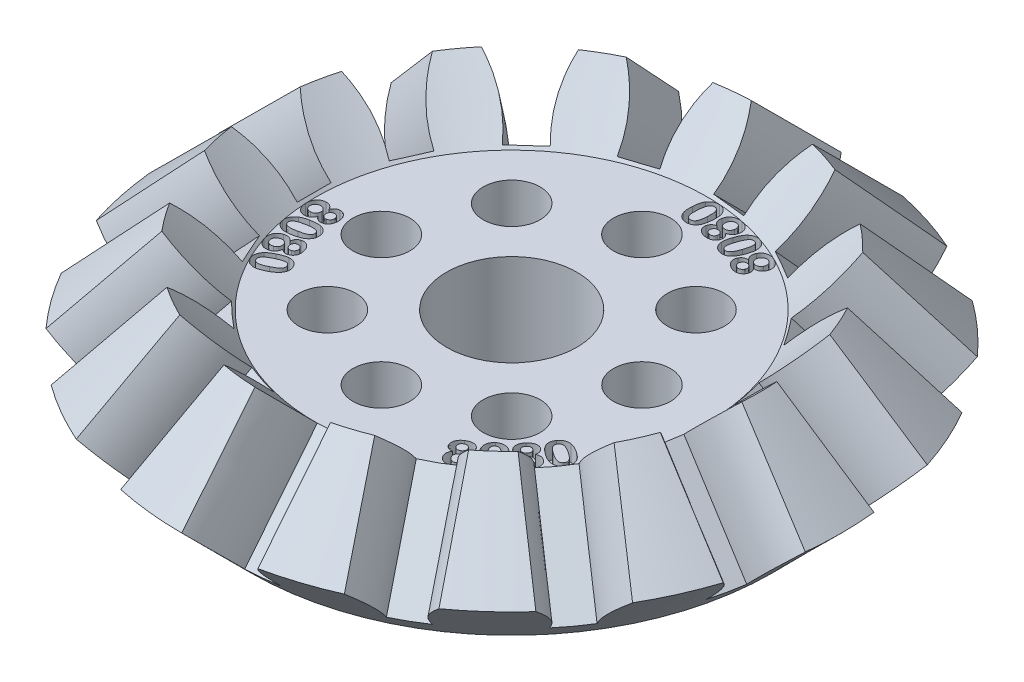
SolidWorks part; units mm, degrees
ref_plane "Front Plane" through (0, 0, 0) normal (0, 0, 1) x (1, 0, 0)
ref_plane "Top Plane" through (0, 0, 0) normal (0, 1, 0) x (1, 0, 0)
ref_plane "Right Plane" through (0, 0, 0) normal (1, 0, 0) x (0, 0, -1)
sketch "Sketch2" plane through (0, 0, 0) normal (0, 0, 1) x (1, 0, 0)
  line L6 (0, 0) -> (0, 6)
  line L7 (0, 0) -> (-16, 0)
  line L8 (0, 6) -> (-12, 6)
  line L9 (-16, 0) -> (-20.2426, 4.2426)
  line L14 (-20.2426, 4.2426) -> (-15.2426, 9.2426)
  line L15 (-12, 6) -> (-15.2426, 9.2426)
  dimension "D1" = 6
  dimension "D2" = 16
  dimension "D3" = 12
  dimension "D4" = 45
  dimension "D5" = 6
revolve "Revolve4" add sketch "Sketch2" angle 360 about L6
sketch "Sketch3" plane through (0, 0, 0) normal (0, 0, 1) x (1, 0, 0)
  line L0 (0, 0) -> (0, 24.4853) construction
  line L1 (0, 24.4853) -> (0, -16.6359) construction
  line L2 (0, 24.4853) -> (-24.6315, -0.1462) construction
  line L3 (-15.2426, 9.2426) -> (-20.2426, 4.2426) construction
  point P7 (0, 0)
ref_plane "Plane1" through (-8, -8, 0) normal (-0.7071, -0.7071, 0) x (0, 0, 1)
sketch "Sketch4" plane through (-8, -8, 0) normal (-0.7071, -0.7071, 0) x (0, 0, 1)
  line L0 (0, 9.4379) -> (0, 20.6725) construction
  line L1 (0, 0) -> (0, 17.3137) construction
  line L2 (-1.0394, 12.9374) -> (1.0394, 12.9374)
  line L3 (2.6025, 17.9681) -> (-2.6025, 17.9681)
  spline S0 degree 2 poles (1.0394, 12.9374) (0.9134, 15.6128) (2.6025, 17.9681) knots 0 0 0 1 1 1
  spline S1 degree 2 poles (-1.0394, 12.9374) (-0.9134, 15.6128) (-2.6025, 17.9681) knots 0 0 0 1 1 1
  point P11 (0, 12.9374)
  point P13 (0, 17.9681)
  dimension "D1" = 2.6025
extrude "Cut-Extrude2" cut sketch "Sketch4" against normal blind 10 contours L3 S1 L2 S0
pattern_circular "CirPattern2" count 15 over 360 about axis through (0, 0, 0) along (0, 1, 0) of "Cut-Extrude2" reverse direction yes
sketch "Sketch5" plane through (0, 6, 0) normal (0, 1, 0) x (1, 0, 0)
  line L0 (0, 0) -> (0, -8)
  circle A0 centre (0, 0) radius 4
  circle A1 centre (0, -8) radius 1.75
  dimension "D1" = 8
  dimension "D3" = 3.5
  dimension "D2" = 8
extrude "Cut-Extrude3" cut sketch "Sketch5" against normal blind 10 contours A0 region at (-2.7484, 6, -2.7484)
extrude "Cut-Extrude4" cut sketch "Sketch5<3>" against normal blind 10 contours A1
sketch "Sketch5<3>" plane through (0, 6, 0) normal (0, 1, 0) x (1, 0, 0) same geometry as "Sketch5"
pattern_circular "CirPattern3" count 8 over 360 about axis through (0, 0, 0) along (0, 1, 0) of "Cut-Extrude4"
sketch "Sketch6" plane through (0, 0, 0) normal (0, -1, 0) x (1, 0, 0)
  text T0 "8080" font "Arial Rounded MT Bold" height 3.175
extrude "Cut-Extrude5" cut sketch "Sketch6" against normal blind 1
pattern_circular "CirPattern4" count 3 over 360 about axis through (0, 24.4853, 0) along (0, -1, 0) of "Cut-Extrude5" reverse direction yes
sketch "Sketch7" plane through (0, 6, 0) normal (0, 1, 0) x (1, 0, 0)
  text T0 "8080" font "Arial Rounded MT Bold" height 2
extrude "Cut-Extrude6" cut sketch "Sketch7" against normal blind 1
pattern_circular "CirPattern5" count 3 over 360 about axis through (0, 0, 0) along (0, 1, 0) of "Cut-Extrude6" reverse direction yes
